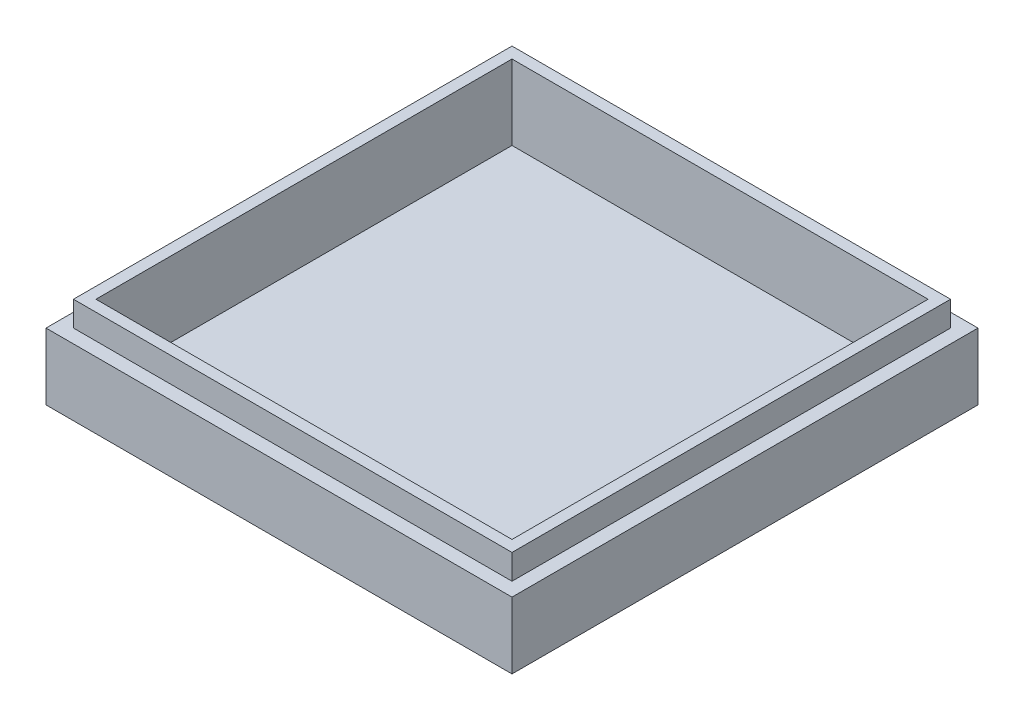
SolidWorks part; units mm, degrees
ref_plane "Front Plane" through (0, 0, 0) normal (0, 0, 1) x (1, 0, 0)
ref_plane "Top Plane" through (0, 0, 0) normal (0, 1, 0) x (1, 0, 0)
ref_plane "Right Plane" through (0, 0, 0) normal (1, 0, 0) x (0, 0, -1)
sketch "Sketch1" plane through (0, 0, 0) normal (0, 1, 0) x (1, 0, 0)
  line L0 (-28, 28) -> (28, 28)
  line L1 (-25, 25) -> (25, 25)
  line L2 (-25, 25) -> (-25, -25)
  line L3 (-25, -25) -> (25, -25)
  line L4 (25, 25) -> (25, -25)
  line L5 (-25, 25) -> (25, -25) construction
  line L6 (-25, -25) -> (25, 25) construction
  line L7 (28, 28) -> (28, -28)
  line L8 (-28, -28) -> (28, -28)
  line L9 (-28, 28) -> (-28, -28)
  point P0 (0, 0)
  dimension "D1" = 50
  dimension "D2" = 3
extrude "Boss-Extrude1" add sketch "Sketch1" against normal blind 2 contours L0 L7 L8 L9
extrude "Boss-Extrude2" add sketch "Sketch1<3>" along normal blind 6
sketch "Sketch1<3>" plane through (0, 0, 0) normal (0, 1, 0) x (1, 0, 0) same geometry as "Sketch1"
sketch "Sketch2" plane through (0, 6, 0) normal (0, 1, 0) x (1, 0, 0)
  line L8 (25, -25) -> (25, 25) construction
  line L9 (-25, -25) -> (25, -25) construction
  line L10 (-25, 25) -> (-25, -25) construction
  line L11 (25, 25) -> (-25, 25) construction
  line L12 (26.35, -26.35) -> (26.35, 26.35)
  line L13 (-26.35, -26.35) -> (26.35, -26.35)
  line L14 (-26.35, 26.35) -> (-26.35, -26.35)
  line L15 (26.35, 26.35) -> (-26.35, 26.35)
  line L16 (26.35, -26.35) -> (26.35, 26.35)
  line L17 (-26.35, -26.35) -> (26.35, -26.35)
  line L18 (-26.35, 26.35) -> (-26.35, -26.35)
  line L19 (26.35, 26.35) -> (-26.35, 26.35)
  line L20 (25, -25) -> (25, 25)
  line L21 (-25, -25) -> (25, -25)
  line L22 (-25, 25) -> (-25, -25)
  line L23 (25, 25) -> (-25, 25)
  dimension "D1" = 1.35
extrude "Boss-Extrude3" add sketch "Sketch2" along normal blind 3
equation "\"D1@Sketch2\"=1.50mm-.15"
